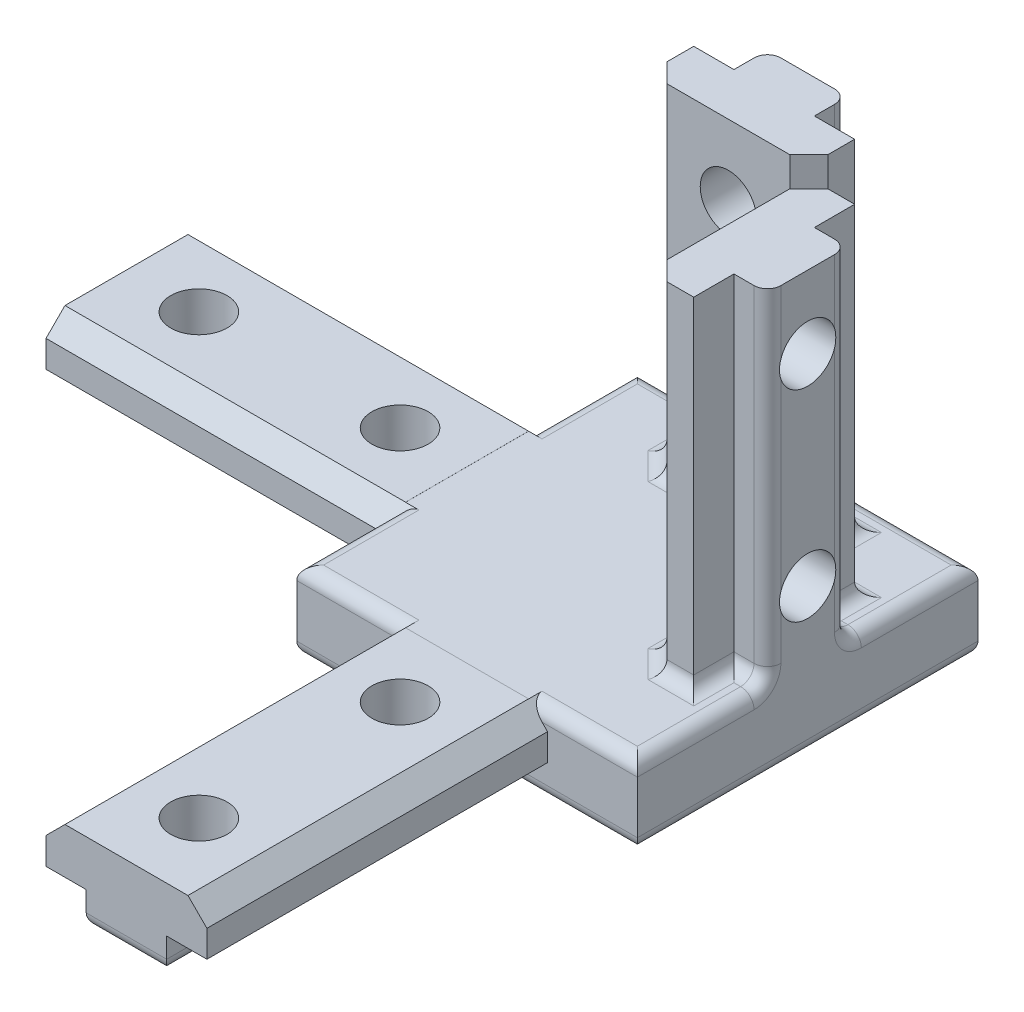
SolidWorks part; units mm, degrees
ref_plane "Front Plane" through (0, 0, 0) normal (0, 0, 1) x (1, 0, 0)
ref_plane "Top Plane" through (0, 0, 0) normal (0, 1, 0) x (1, 0, 0)
ref_plane "Right Plane" through (0, 0, 0) normal (1, 0, 0) x (0, 0, -1)
sketch "Sketch1" plane through (0, 0, 0) normal (0, 1, 0) x (1, 0, 0)
  line L1 (-12.7, 12.7) -> (12.7, 12.7)
  line L2 (-12.7, 12.7) -> (-12.7, -12.7)
  line L3 (-12.7, -12.7) -> (12.7, -12.7)
  line L4 (12.7, 12.7) -> (12.7, -12.7)
  line L5 (-12.7, 12.7) -> (12.7, -12.7) construction
  line L6 (-12.7, -12.7) -> (12.7, 12.7) construction
  point P0 (0, 0)
  dimension "D1" = 25.4
extrude "Boss-Extrude1" add sketch "Sketch1" along normal blind 5.91
sketch "Sketch2" plane through (0, 0, 12.7) normal (0, 0, 1) x (1, 0, 0)
  line L0 (-3, 0) -> (3, 0)
  line L1 (-12.7, 0) -> (12.7, 0) construction
  line L2 (3, 0) -> (3, 2.5)
  line L3 (3, 2.5) -> (6, 2.5)
  line L4 (6, 2.5) -> (6, 4.5)
  line L5 (6, 4.5) -> (4.5858, 5.9142)
  line L6 (4.5858, 5.9142) -> (-4.5858, 5.9142)
  line L7 (0, 0) -> (0, 6.6193) construction
  line L8 (-6, 4.5) -> (-4.5858, 5.9142)
  line L9 (-6, 2.5) -> (-6, 4.5)
  line L10 (-3, 2.5) -> (-6, 2.5)
  line L11 (-3, 0) -> (-3, 2.5)
  point P14 (0, 5.9142)
  point P18 (0, 0)
  dimension "D1" = 6
  dimension "D2" = 12
  dimension "D3" = 135
  dimension "D4" = 2.5
  dimension "D5" = 2
extrude "Boss-Extrude2" add sketch "Sketch2" along normal blind 25.4
sketch "Sketch3" plane through (-12.7, 0, 0) normal (-1, 0, 0) x (0, 0, 1)
  line L0 (-3, 0) -> (3, 0)
  line L1 (3, 0) -> (3, 2.5)
  line L2 (3, 2.5) -> (6, 2.5)
  line L3 (6, 2.5) -> (6, 4.5)
  line L4 (6, 4.5) -> (4.5858, 5.9142)
  line L5 (4.5858, 5.9142) -> (-4.5858, 5.9142)
  line L6 (0, 0) -> (0, 6.6193) construction
  line L7 (-6, 4.5) -> (-4.5858, 5.9142)
  line L8 (-6, 2.5) -> (-6, 4.5)
  line L9 (-3, 2.5) -> (-6, 2.5)
  line L10 (-3, 0) -> (-3, 2.5)
  point P9 (0, 5.9142)
  point P13 (0, 0)
  dimension "D1" = 6
  dimension "D2" = 12
  dimension "D3" = 2.5
  dimension "D4" = 2
  dimension "D5" = 135
extrude "Boss-Extrude3" add sketch "Sketch3" along normal blind 25.4
sketch "Sketch5" plane through (0, 5.91, 0) normal (0, 1, 0) x (1, 0, 0)
  line L0 (3, 12.7) -> (-3, 12.7)
  line L1 (-3, 12.7) -> (-3, 10.2)
  line L2 (-3, 10.2) -> (-6, 10.2)
  line L3 (-6, 10.2) -> (-6, 8.2)
  line L4 (-6, 8.2) -> (-4.5858, 6.7858)
  line L5 (-4.5858, 6.7858) -> (4.5858, 6.7858)
  line L6 (0, 3.4686) -> (0, -3.1261) construction
  line L7 (6, 8.2) -> (4.5858, 6.7858)
  line L8 (6, 10.2) -> (6, 8.2)
  line L9 (3, 10.2) -> (6, 10.2)
  line L10 (3, 12.7) -> (3, 10.2)
  line L11 (12.7, 12.7) -> (-12.7, 12.7) construction
  line L12 (12.7, -3) -> (12.7, 3)
  line L13 (12.7, 3) -> (10.2, 3)
  line L14 (10.2, 3) -> (10.2, 6)
  line L15 (10.2, 6) -> (8.2, 6)
  line L16 (8.2, 6) -> (6.7858, 4.5858)
  line L17 (6.7858, 4.5858) -> (6.7858, -4.5858)
  line L18 (6.7858, 0) -> (12.7, 0) construction
  line L19 (8.2, -6) -> (6.7858, -4.5858)
  line L20 (10.2, -6) -> (8.2, -6)
  line L21 (10.2, -3) -> (10.2, -6)
  line L22 (12.7, -3) -> (10.2, -3)
  line L23 (12.7, -12.7) -> (12.7, 12.7) construction
  point P9 (0, 6.7858)
  point P13 (0, 12.7)
  point P27 (6.7858, 0)
  point P31 (12.7, 0)
  dimension "D1" = 6
  dimension "D2" = 12
  dimension "D3" = 2.5
  dimension "D4" = 2
  dimension "D5" = 135
  dimension "D6" = 2.5
  dimension "D7" = 6
  dimension "D8" = 12
  dimension "D9" = 2
  dimension "D10" = 135
  dimension "D11" = 135
extrude "Boss-Extrude4" add sketch "Sketch5" along normal blind 25.4
fillet "Fillet2" radius 1 42 edges at (3, 18.61, -12.7) (12.7, 18.61, -3) (12.7, 18.61, 3) (-3, 18.61, -12.7) (-6, 5.91, -9.2) (-5.2929, 5.91, -7.4929) (0, 5.91, -6.7858) (5.2929, 5.91, -7.4929) (6, 5.91, -9.2) (4.5, 5.91, -10.2) (3, 5.91, -11.45) (7.85, 5.91, -12.7) (12.7, 5.91, -7.85) (11.45, 5.91, -3) (10.2, 5.91, -4.5) (9.2, 5.91, -6) (7.4929, 5.91, -5.2929) (6.7858, 5.91, 0) (7.4929, 5.91, 5.2929) (9.2, 5.91, 6) (10.2, 5.91, 4.5) (11.45, 5.91, 3) (12.7, 5.91, 7.85) (8.645, 5.91, 12.7) (-8.645, 5.91, 12.7) (-12.7, 5.91, 8.645) (-12.7, 5.91, -8.645) (-7.85, 5.91, -12.7) (-3, 5.91, -11.45) (-4.5, 5.91, -10.2) (0, 0, -12.7) (-12.7, 0, -7.85) (-25.4, 0, -3) (-38.1, 0, 0) (-25.4, 0, 3) (-12.7, 0, 7.85) (-7.85, 0, 12.7) (-3, 0, 25.4) (0, 0, 38.1) (3, 0, 25.4) (7.85, 0, 12.7) (12.7, 0, 0)
hole_wizard "M5x0.8 Tapped Hole2" positions "Sketch8" profile "Sketch9" tap size "M5x0.8" standard "ANSI Metric" end condition through all
sketch "Sketch8" plane through (0, 0, 0) normal (0, -1, 0) x (-1, 0, 0)
  line L0 (12.7, 6) -> (12.7, 3) construction
  line L1 (6, -12.7) -> (3, -12.7) construction
  point P0 (0, -17.7)
  point P2 (0, -32.7)
  point P4 (17.7, 0)
  point P6 (32.7, 0)
  dimension "D1" = 5
  dimension "D2" = 15
  dimension "D3" = 5
  dimension "D4" = 15
sketch "Sketch9" plane through (0, 0, 17.7) normal (1, 0, 0) x (0, 0, -1)
  line L0 (0, 0) -> (0, 31.31)
  line L1 (0, 31.31) -> (2.1, 31.31)
  line L2 (2.1, 31.31) -> (2.1, 0)
  line L5 (2.1, 0) -> (0, 0)
  line L11 (0, -6.35) -> (0, 107.95) construction
  dimension "Thru Tap Drill Dia." = 4.2
  dimension "Thru Tap Drill Depth" = 31.31
cosmetic thread "Hole Thread3" parameters "D2"=5
cosmetic thread "Hole Thread4" parameters "D2"=5
cosmetic thread "Hole Thread5" parameters "D2"=5
cosmetic thread "Hole Thread6" parameters "D2"=5
hole_wizard "M5x0.8 Tapped Hole3" positions "Sketch10" profile "Sketch11" tap size "M5x0.8" standard "ANSI Metric" end condition through all
sketch "Sketch10" plane through (12.7, 0, 0) normal (1, 0, 0) x (0, 0, -1)
  line L0 (-4, 5.91) -> (-7, 5.91) construction
  point P0 (0, 10.91)
  point P2 (0, 25.91)
  dimension "D1" = 5
  dimension "D2" = 15
sketch "Sketch11" plane through (12.7, 10.91, 0) normal (0, 1, 0) x (0, 0, -1)
  line L0 (0, 0) -> (0, 50.8)
  line L1 (0, 50.8) -> (2.1, 50.8)
  line L2 (2.1, 50.8) -> (2.1, 0)
  line L5 (2.1, 0) -> (0, 0)
  line L11 (0, -6.35) -> (0, 107.95) construction
  dimension "Thru Tap Drill Dia." = 4.2
  dimension "Thru Tap Drill Depth" = 50.8
cosmetic thread "Hole Thread7" parameters "D2"=5
cosmetic thread "Hole Thread8" parameters "D2"=5
hole_wizard "M5x0.8 Tapped Hole4" positions "Sketch12" profile "Sketch13" tap size "M5x0.8" standard "ANSI Metric" end condition through all
sketch "Sketch12" plane through (0, 0, -12.7) normal (0, 0, -1) x (-1, 0, 0)
  line L0 (-4, 5.91) -> (-7, 5.91) construction
  point P0 (0, 25.91)
  point P2 (0, 10.91)
  dimension "D1" = 5
  dimension "D2" = 15
sketch "Sketch13" plane through (0, 25.91, -12.7) normal (1, 0, 0) x (0, 1, 0)
  line L0 (0, 0) -> (0, 50.8)
  line L1 (0, 50.8) -> (2.1, 50.8)
  line L2 (2.1, 50.8) -> (2.1, 0)
  line L5 (2.1, 0) -> (0, 0)
  line L11 (0, -6.35) -> (0, 107.95) construction
  dimension "Thru Tap Drill Dia." = 4.2
  dimension "Thru Tap Drill Depth" = 50.8
cosmetic thread "Hole Thread9" parameters "D2"=5
cosmetic thread "Hole Thread10" parameters "D2"=5
equation "\"Insert Lengths\"= 1in"
equation "\"D1@Boss-Extrude2\"=\"Insert Lengths\""
equation "\"D1@Boss-Extrude4\"=\"Insert Lengths\""
